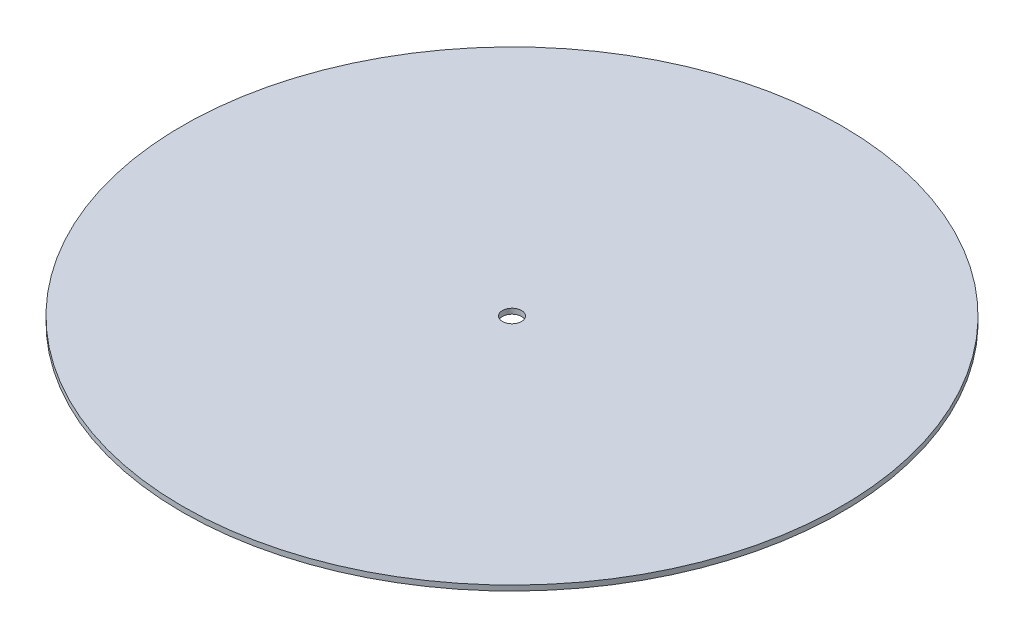
SolidWorks part; units mm, degrees
ref_plane "前视基准面" through (0, 0, 0) normal (0, 0, 1) x (1, 0, 0)
ref_plane "上视基准面" through (0, 0, 0) normal (0, 1, 0) x (1, 0, 0)
ref_plane "右视基准面" through (0, 0, 0) normal (1, 0, 0) x (0, 0, -1)
sketch "草图1" plane through (0, 0, 0) normal (0, 1, 0) x (1, 0, 0)
  circle A0 centre (0, 0) radius 190
  dimension "D1" = 380
extrude "凸台-拉伸1" add sketch "草图1" along normal blind 3
ref_axis "旋转轴" through (0, 3, 0) along (0, -1, 0)
hole_wizard "Ø11.0 (11) 直径孔1" positions "草图2" profile "草图3" hole size "Ø11.0" standard "ISO" end condition up to next
sketch "草图2" plane through (0, 3, 0) normal (0, 1, 0) x (1, 0, 0)
  point P0 (0, 0)
sketch "草图3" plane through (0, 3, 0) normal (1, 0, 0) x (0, 0, 1)
  line L0 (0, 0) -> (0, 3)
  line L1 (0, 3) -> (5.5, 3)
  line L2 (5.5, 3) -> (5.5, 0)
  line L5 (5.5, 0) -> (0, 0)
  line L11 (0, -6.35) -> (0, 107.95) construction
  dimension "通孔孔直径" = 11
  dimension "通孔孔深度" = 3
